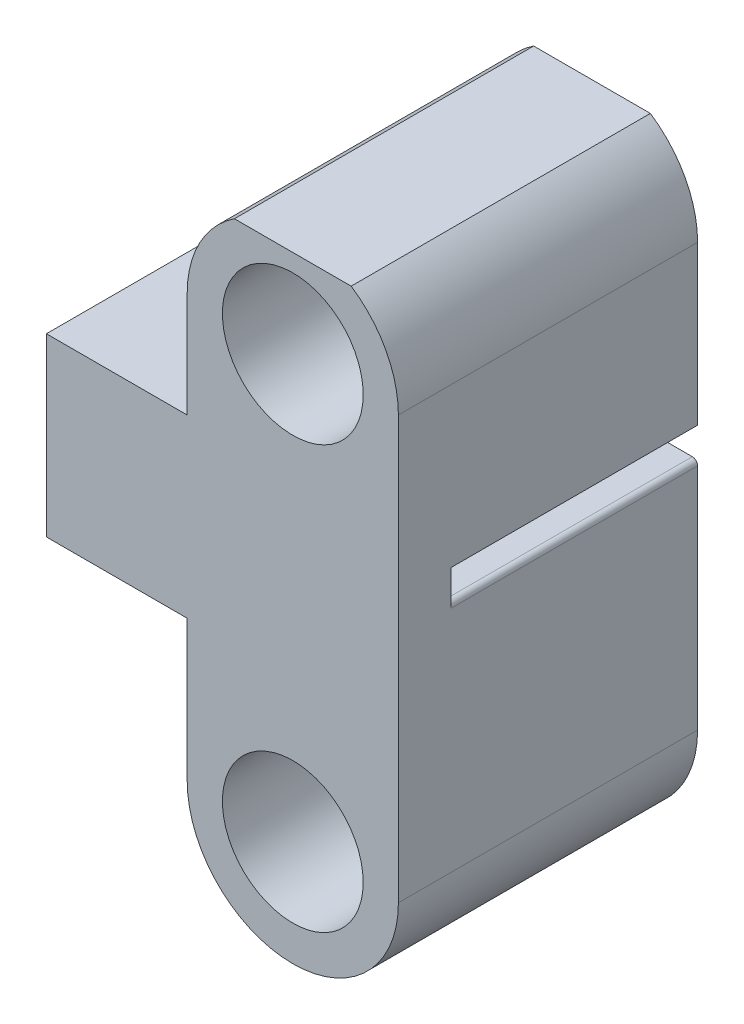
SolidWorks part; units mm, degrees
ref_plane "Front Plane" through (0, 0, 0) normal (0, 0, 1) x (1, 0, 0)
ref_plane "Top Plane" through (0, 0, 0) normal (0, 1, 0) x (1, 0, 0)
ref_plane "Right Plane" through (0, 0, 0) normal (1, 0, 0) x (0, 0, -1)
sketch "Sketch1" plane through (0, 0, 0) normal (0, 0, 1) x (1, 0, 0)
  line L0 (0, 0) -> (0, -12) construction
  line L1 (-3, 0) -> (-3, -12)
  line L2 (3, 0) -> (3, -12)
  arc A0 (3, 0) -> (-3, 0) centre (0, 0) ccw
  arc A1 (-3, -12) -> (3, -12) centre (0, -12) ccw
  circle A2 centre (0, 0) radius 2
  circle A3 centre (0, -12) radius 2
  dimension "D2" = 6
  dimension "D6" = 4
  dimension "D7" = 4
  dimension "D1" = 12
extrude "Boss-Extrude1" add sketch "Sketch1" along normal blind 8.5
sketch "Sketch2" plane through (3, 0, 0) normal (1, 0, 0) x (0, 0, -1)
  line L0 (-8.5, -6) -> (0, -6) construction
  line L1 (-8.5, -12) -> (-8.5, 0) construction
  line L2 (0, -12) -> (0, 0) construction
  line L3 (-4.25, 0) -> (-4.25, -12) construction
  line L4 (-8.5, 0) -> (0, 0) construction
  line L5 (-8.5, -12) -> (0, -12) construction
  circle A0 centre (-4.25, -8.5) radius 2
  dimension "D1" = 4
  dimension "D2" = 2.5
extrude "Cut-Extrude1" [suppressed] cut sketch "Sketch2" against normal through all
sketch "Sketch3" [suppressed] plane through (3, 0, 0) normal (1, 0, 0) x (0, 0, -1)
  line L1 (-0.6416, -8.5) -> (-2.4458, -5.375)
  line L2 (-2.4458, -5.375) -> (-6.0542, -5.375)
  line L3 (-6.0542, -5.375) -> (-7.8584, -8.5)
  line L4 (-7.8584, -8.5) -> (-6.0542, -11.625)
  line L5 (-6.0542, -11.625) -> (-2.4458, -11.625)
  line L6 (-2.4458, -11.625) -> (-0.6416, -8.5)
  line L7 (-1.8684, -4.375) -> (-6.6316, -4.375)
  line L8 (-6.6316, -4.375) -> (-9.0131, -8.5)
  line L9 (-9.0131, -8.5) -> (-6.6316, -12.625)
  line L10 (-6.6316, -12.625) -> (-1.8684, -12.625)
  line L11 (-1.8684, -12.625) -> (0.5131, -8.5)
  line L12 (0.5131, -8.5) -> (-1.8684, -4.375)
  circle A0 centre (-4.25, -8.5) radius 3.125 construction
  circle A1 centre (-4.25, -8.5) radius 4.125 construction
  dimension "D1" = 6.25
  dimension "D2" = 1
extrude "Boss-Extrude2" [suppressed] add sketch "Sketch3" along normal blind 2 and the other way blind 0.5
sketch "Sketch4" [suppressed] plane through (-3, 0, 0) normal (-1, 0, 0) x (0, 0, 1)
  line L0 (4.25, 0) -> (4.25, -6.5) construction
  line L1 (8.5, 0) -> (0, 0) construction
  line L3 (0.75, -2.75) -> (7.75, -2.75)
  line L4 (0.75, -2.75) -> (0.75, -5.75)
  line L5 (0.75, -5.75) -> (7.75, -5.75)
  line L6 (7.75, -2.75) -> (7.75, -5.75)
  line L7 (0.75, -2.75) -> (7.75, -5.75) construction
  line L8 (0.75, -5.75) -> (7.75, -2.75) construction
  circle A0 centre (4.25, -8.5) radius 2 construction
  point P7 (4.25, -4.25)
  dimension "D1" = 7
  dimension "D2" = 3
  dimension "D3" = 2.75
extrude "Cut-Extrude2" [suppressed] cut sketch "Sketch4" against normal through all
sketch "Sketch5" plane through (-3, 0, 0) normal (-1, 0, 0) x (0, 0, 1)
  line L0 (4.25, 0) -> (4.25, -12) construction
  line L1 (8.5, 0) -> (0, 0) construction
  line L2 (8.5, -12) -> (0, -12) construction
  line L3 (0, -6) -> (8.5, -6) construction
  line L4 (0, 0) -> (0, -12) construction
  line L5 (8.5, 0) -> (8.5, -12) construction
  line L7 (0, -15) -> (8.5, -15)
  line L8 (0, -15) -> (0, 3)
  line L9 (0, 3) -> (8.5, 3)
  line L10 (8.5, -15) -> (8.5, 3)
  line L11 (0, -15) -> (8.5, 3) construction
  line L12 (0, 3) -> (8.5, -15) construction
  point P12 (4.25, -6)
extrude "Cut-Extrude3" [suppressed] cut sketch "Sketch5" against normal through all flip side to cut
sketch "Sketch9" plane through (-3, 0, 0) normal (-1, 0, 0) x (0, 0, 1)
  line L0 (8.5, 0) -> (8.5, -12) construction
  line L1 (0, -3) -> (8.5, -3)
  line L2 (0, -3) -> (0, -8)
  line L3 (0, -8) -> (8.5, -8)
  line L4 (8.5, -3) -> (8.5, -8)
  line L5 (0, 0) -> (0, -12) construction
  line L6 (8.5, 0) -> (0, 0) construction
  dimension "D1" = 5
  dimension "D2" = 3
extrude "Boss-Extrude4" add sketch "Sketch9" along normal blind 4
sketch "Sketch6" plane through (3, 0, 0) normal (1, 0, 0) x (0, 0, -1)
  line L0 (0, -12) -> (0, 0) construction
  line L1 (0, -4.5) -> (-7, -4.5)
  line L2 (0, -4.5) -> (0, -6.1)
  line L3 (0, -6.1) -> (-7, -6.1)
  line L4 (-7, -4.5) -> (-7, -6.1)
  dimension "D1" = 1.6
  dimension "D2" = 4.5
  dimension "D3" = 7
extrude "Cut-Extrude5" cut sketch "Sketch6" against normal through all
sketch "Sketch7" plane through (0, 0, 7) normal (0, 0, -1) x (-1, 0, 0)
  line L0 (-3, -6.1) -> (-3, -5.5)
  line L1 (-3, -4.5) -> (-3, -6.1) construction
  line L2 (-2.85, -5.35) -> (-2.15, -5.35)
  line L3 (-2, -5.5) -> (-2, -6.1)
  line L4 (7, -6.1) -> (-3, -6.1) construction
  line L5 (-2, -6.1) -> (-3, -6.1)
  line L6 (-0.85, -5.35) -> (-0.15, -5.35)
  line L7 (0, -5.5) -> (0, -6.1)
  line L8 (0, -6.1) -> (-1, -6.1)
  line L9 (-1, -6.1) -> (-1, -5.5)
  line L10 (1.15, -5.35) -> (1.85, -5.35)
  line L11 (2, -5.5) -> (2, -6.1)
  line L12 (2, -6.1) -> (1, -6.1)
  line L13 (1, -6.1) -> (1, -5.5)
  line L14 (3.15, -5.35) -> (3.85, -5.35)
  line L15 (4, -5.5) -> (4, -6.1)
  line L16 (4, -6.1) -> (3, -6.1)
  line L17 (3, -6.1) -> (3, -5.5)
  line L18 (5.15, -5.35) -> (5.85, -5.35)
  line L19 (6, -5.5) -> (6, -6.1)
  line L20 (6, -6.1) -> (5, -6.1)
  line L21 (5, -6.1) -> (5, -5.5)
  arc A0 (-2.15, -5.35) -> (-2, -5.5) centre (-2.15, -5.5) cw
  arc A1 (-3, -5.5) -> (-2.85, -5.35) centre (-2.85, -5.5) cw
  arc A2 (-1, -5.5) -> (-0.85, -5.35) centre (-0.85, -5.5) cw
  arc A3 (-0.15, -5.35) -> (0, -5.5) centre (-0.15, -5.5) cw
  arc A4 (1, -5.5) -> (1.15, -5.35) centre (1.15, -5.5) cw
  arc A5 (1.85, -5.35) -> (2, -5.5) centre (1.85, -5.5) cw
  arc A6 (3, -5.5) -> (3.15, -5.35) centre (3.15, -5.5) cw
  arc A7 (3.85, -5.35) -> (4, -5.5) centre (3.85, -5.5) cw
  arc A8 (5, -5.5) -> (5.15, -5.35) centre (5.15, -5.5) cw
  arc A9 (5.85, -5.35) -> (6, -5.5) centre (5.85, -5.5) cw
  point P11 (-2, -5.35)
  point P14 (-3, -5.35)
  dimension "D3" = 0.15
  dimension "D1" = 1
  dimension "D2" = 0.75
  dimension "D4" = 5
extrude "Boss-Extrude3" add sketch "Sketch7" along normal through all
sketch "Sketch10" plane through (0, 0, 8.5) normal (0, 0, 1) x (1, 0, 0)
  line L1 (-2.5, 3.5) -> (2.5, 3.5)
  line L2 (-2.5, 3.5) -> (-2.5, 2.5)
  line L3 (-2.5, 2.5) -> (2.5, 2.5)
  line L4 (2.5, 3.5) -> (2.5, 2.5)
  line L5 (-2.5, 3.5) -> (2.5, 2.5) construction
  line L6 (-2.5, 2.5) -> (2.5, 3.5) construction
  arc A0 (3, 0) -> (-3, 0) centre (0, 0) ccw construction
  point P0 (0, 3)
  dimension "D1" = 1
  dimension "D2" = 5
extrude "Cut-Extrude6" cut sketch "Sketch10" against normal through all
equation "\"X-ROD-SPACING\"=45"
equation "\"Y-ROD-SPACING\"=75"
equation "\"Z-ROD-SPACING\"=17.5"
equation "\"Y-BED-OFFSET\"=2"
equation "\"Y-BED-ROD-INSET\"=3.5"
equation "\"Y-BED-SCREW-SPACING\"=209"
equation "\"Y-BED-SCREW-CUTOUT-SLOT-HEIGHT\"=2"
equation "\"T-SLOT-NUT-FILLET-RADIUS\"=0.25"
equation "\"T-SLOT-SCREW-SHAFT-RADIUS\"=1.75"
equation "\"T-SLOT-SCREW-SHAFT-CUTOUT-LENGTH\"=10.5"
equation "\"T-SLOT-NUT-DEPTH\"=4.2"
equation "\"T-SLOT-NUT-WIDTH\"=3"
equation "\"T-SLOT-NUT-END-DISTANCE\"=8"
equation "\"ACRYLIC-THICKNESS\"=10"
equation "\"ACRYLIC-THICKNESS2\"=4.5"
equation "\"ACRYLIC-TAB-CUTOUT-SIZE\"=\"ACRYLIC-THICKNESS\"+\"ACRYLIC-TAB-TOLERANCE\"*2"
equation "\"ACRYLIC-TAB-TOLERANCE\"=.1"
equation "\"ACRYLIC-TAB-WIDTH\"=\"ACRYLIC-THICKNESS\""
equation "\"ACRYLIC-M3-HOLE\"=3.1"
equation "\"SMOOTHROD-CAP-SCREW-DISTANCE\"=20"
equation "\"FRAME-WIDTH-INNER\"=370"
equation "\"NEMA17-HOLE-SPACING\"=31"
equation "\"NEMA17-CENTRAL-CUTOUT\"=22.5"
equation "\"Z-BRACKET-REACH\"=55"
equation "\"Z-ROD-INSET\"=16"
equation "\"TOP-BRACKET-SPACING\"=40"
equation "\"SMOOTHROD-X-LENGTH\"=350"
equation "\"SMOOTHROD-Y-LENGTH\"=350"
equation "\"SMOOTHROD-Z-LENGTH\"=350"
equation "\"SMOOTHROD-TIGHTENING-HEADROOM\"=.25"
equation "\"LEADSCREW-Z-LENGTH\"=300"
equation "\"SCREW-LENGTH-FRAME\"=\"ACRYLIC-THICKNESS\" + 10"
equation "\"SCREW-LENGTH-MOTOR\"=\"ACRYLIC-THICKNESS\" + 5"
equation "\"SCREW-LENGTH-EXTRUDER\"=28"
equation "\"SCREW-HEAD-RADIUS\"=6"
equation "\"PRINTED-M3-HOLE\"=3.5"
equation "\"PRINTED-X-SMOOTHROD-DIAMETER\"=8.2"
equation "\"PRINTED-X-SMOOTHROD-CUTOUT\"=10"
equation "\"PRINTED-X-BASE-HEIGHT\"=10"
equation "\"PRINTED-LM8UU-CUTOUT-SIZE\"=15.25"
equation "\"PRINTED-LM8UU-CUTOUT-LENGTH\"=24.5"
equation "\"PRINTED-X-IDLER-HEIGHT\"=16"
equation "\"PRINTED-M3-NUT-AF\"=6.25"
equation "\"PSU-MOUNTING-WIDTH\"=95"
equation "\"PSU-MOUNTING-HEIGHT\"=177"
equation "\"Y-BELT-TO-ROD-DISTANCE\"=20"
equation "\"SPOOL-HOLDER-ROD-SPACING\"=150"
equation "\"ACRYLIC-X-CARRIAGE-WIDTH\"=55"
equation "\"ACRYLIC-X-CARRIAGE-HEIGHT\"=75"
equation "\"ACRYLIC-X-CARRIAGE-LM8UU-CUTOUT-WIDTH\"=24.25"
equation "\"ACRYLIC-X-CARRIAGE-LM8UU-CUTOUT-HEIGHT\"=11.5"
equation "\"ACRYLIC-X-CARRIAGE-SCREW-SPACING-X\"=15"
equation "\"ACRYLIC-X-CARRIAGE-SCREW-SPACING-Y\"=33"
equation "\"ACRYLIC-X-CARRIAGE-CENTER-TAB-SPACING\"=14"
equation "\"ACRYLIC-X-CARRIAGE-EXTRUDER-OFFSET\"=26"
equation "\"ACRYLIC-X-CARRIAGE-EXTRUDER-ANGLE\"=90"
equation "\"ACRYLIC-X-CARRIAGE-EXTRUDER-SHELF-DEPTH\"=\"ACRYLIC-X-CARRIAGE-EXTRUDER-OFFSET\" + 28"
equation "\"ACRYLIC-X-CARRIAGE-EXTRUDER-BRACE-SPACING\"=23"
equation "\"ACRYLIC-X-CARRIAGE-EXTRUDER-BRACE-TAB-OFFSET\"=20"
equation "\"ACRYLIC-X-CARRIAGE-EXTRUDER-BRACE-HEIGHT\"=35"
equation "\"ACRYLIC-X-CARRIAGE-EXTRUDER-BRACE-SCREW-SPACING\"=22"
equation "\"ACRYLIC-X-CARRIAGE-DUAL-WIDTH-MULTIPLIER\"=1.65"
equation "\"ACRYLIC-X-CARRIAGE-DUAL-HOTEND-SPACING\"=42"
equation "\"ACRYLIC-X-CARRIAGE-DUAL-WIDTH\"=75"
equation "\"ACRYLIC-X-CARRIAGE-DUAL-HOTEND-SEPARATION\"=36"
equation "\"ACRYLIC-X-CARRIAGE-DUAL-MOUNT-PLATE-DEPTH\"=75"
equation "\"ACRYLIC-X-CARRIAGE-DUAL-MOUNT-BRACE-WIDTH\"=33"
equation "\"ACRYLIC-X-CARRIAGE-DUAL-MOUNT-SCREW-WIDTH\"=40"
equation "\"BLOWER-FAN-WIDTH\"=15"
equation "\"D1@Sketch3\"=\"PRINTED-M3-NUT-AF\""
